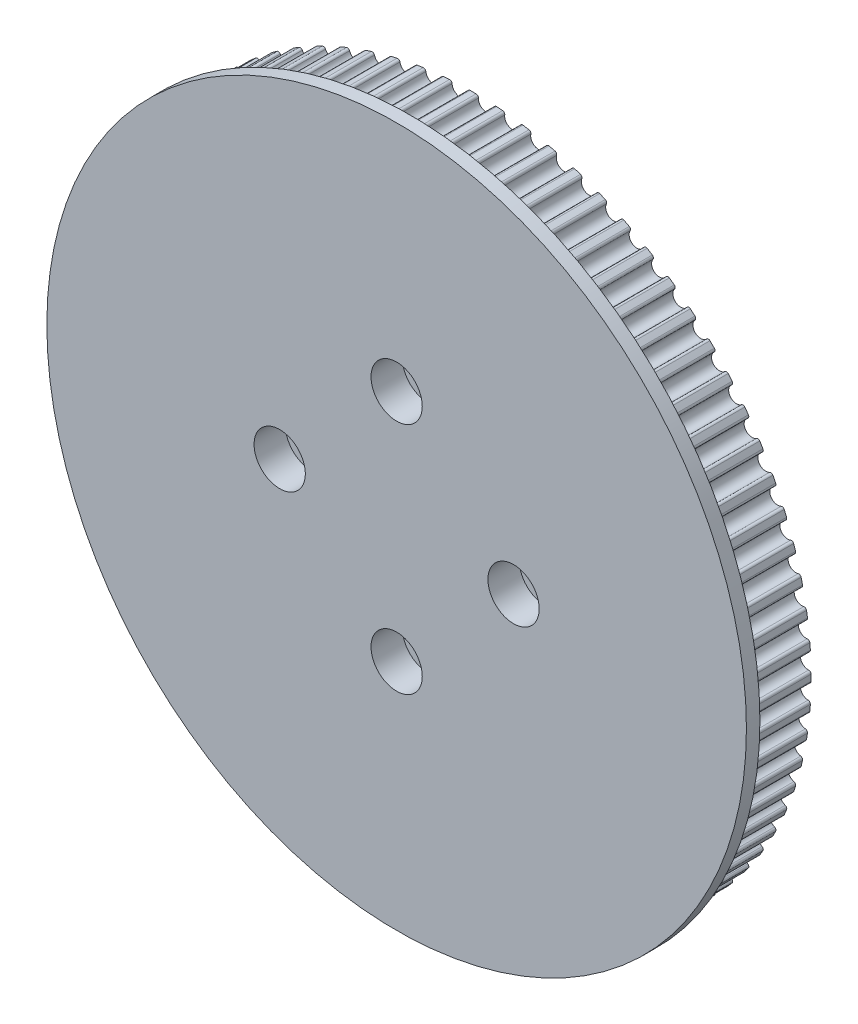
SolidWorks part; units mm, degrees
ref_plane "Front Plane" through (0, 0, 0) normal (1, 0, 0) x (0, 1, 0)
ref_plane "Top Plane" through (0, 0, 0) normal (0, 0, 1) x (0, 1, 0)
ref_plane "Right Plane" through (0, 0, 0) normal (0, 1, 0) x (-1, 0, 0)
sketch "Sketch1" plane through (0, 0, 0) normal (0, 0, 1) x (0, 1, 0)
  line L0 (0, 0) -> (0, 37.5872)
  line L1 (0, 0) -> (1.4297, 36.3891) construction
  line L2 (1.4297, 36.3891) -> (1.4639, 37.2584) construction
  line L3 (0, 0) -> (2.9491, 37.4713)
  arc A3 (0.6561, 37.5815) -> (2.2946, 37.5171) centre (1.4639, 37.2584) ccw
  arc A4 (0, 37.5872) -> (0.6561, 37.5815) centre (0, 0) cw
  arc A5 (2.9491, 37.4713) -> (2.2946, 37.5171) centre (0, 0) ccw
  dimension "D1" = 2.25
  dimension "D2" = 37.5872
  dimension "D3" = 36.4172
  dimension "D4" = 0.87
extrude "Boss-Extrude1" add sketch "Sketch1" along normal blind 7 contours L0 A4 A3 A5 L3
fillet "Fillet1" radius 0.26 2 edges at (-37.5815, 0.6561, 3.5) (-37.5171, 2.2946, 3.5)
pattern_circular "CirPattern1" count 80 over 360 about axis through (0, 0, 7) along (0, 0, -1) of "Fillet1", "Boss-Extrude1" reverse direction yes
sketch "Sketch2" plane through (0, 0, 7) normal (0, 0, 1) x (1, 0, 0)
  circle A1 centre (0, 0) radius 38.8897
  dimension "D2" = 77.7794
extrude "Boss-Extrude2" add sketch "Sketch2" along normal blind 1.5
sketch "Sketch3" plane through (0, 0, 0) normal (0, 0, -1) x (1, 0, 0)
  circle A1 centre (0, 0) radius 21
  dimension "D2" = 42
extrude "Boss-Extrude3" add sketch "Sketch3" along normal blind 1 contours A1
sketch "Sketch4" plane through (0, 0, 8.5) normal (0, 0, 1) x (1, 0, 0)
  circle A0 centre (0, 0) radius 13 construction
  circle A1 centre (0, 13) radius 1.6
  circle A6 centre (0, 13) radius 2.85
  circle A7 centre (13, 0) radius 2.85
  circle A8 centre (13, 0) radius 1.6
  circle A9 centre (0, -13) radius 2.85
  circle A10 centre (0, -13) radius 1.6
  circle A11 centre (-13, 0) radius 2.85
  circle A12 centre (-13, 0) radius 1.6
  point P18 (0, 0)
  dimension "D1" = 26
  dimension "D2" = 3.2
  dimension "D3" = 5.7
extrude "Cut-Extrude3" cut sketch "Sketch4" against normal through all contours A1 | A10 | A12 | A8 region at (0, 13, 8.5) region at (13, 0, 8.5) region at (0, -13, 8.5) region at (-13, 0, 8.5)
extrude "Cut-Extrude4" cut sketch "Sketch4<3>" against normal blind 3.5
sketch "Sketch4<3>" plane through (0, 0, 8.5) normal (0, 0, 1) x (1, 0, 0) same geometry as "Sketch4"
equation "\"D1@Sketch1\"=360 / \"Teeth\" / 2"
equation "\"Teeth\"= 80"
equation "\"D2@Sketch1\"= \"Teeth\" * 3 / 2 / PI - 0.61"
equation "\"D3@Sketch1\"=\"D2@Sketch1\" - 1.17"
equation "\"D4@Sketch1\"=1.74/2"
equation "\"D2@Sketch2\"=\"Teeth\" * 3 / PI - 0.615 + 2"
